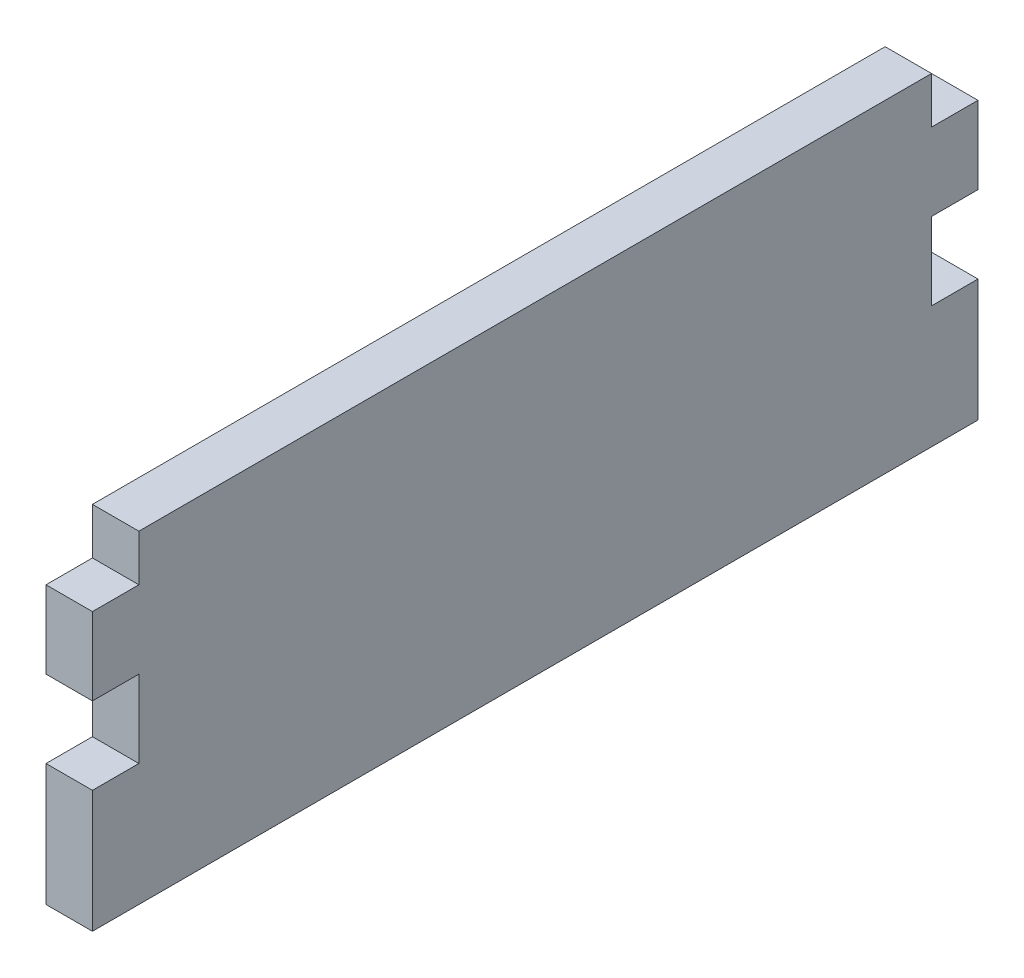
SolidWorks part; units mm, degrees
ref_plane "Спереди" through (0, 0, 0) normal (0, 0, 1) x (1, 0, 0)
ref_plane "Сверху" through (0, 0, 0) normal (0, 1, 0) x (1, 0, 0)
ref_plane "Справа" through (0, 0, 0) normal (1, 0, 0) x (0, 0, -1)
sketch "Эскиз1" plane through (0, 0, 0) normal (1, 0, 0) x (0, 0, -1)
  line L0 (-142.5825, -84.6816) -> (-136.5825, -84.6816) construction
  line L1 (-2.9825, -73.2482) -> (-105.4125, -73.2482) construction
  line L2 (7.7798, -91.3916) -> (7.7798, -95.3916) construction
  line L3 (-111.4125, -137.1716) -> (3.0175, -137.1716)
  line L4 (-2.9825, -95.3916) -> (-105.4125, -95.3916)
  line L5 (-105.4125, -95.3916) -> (-105.4125, -101.3916)
  line L6 (-105.4125, -101.3916) -> (-111.4125, -101.3916)
  line L14 (3.0175, -87.9576) -> (-2.9825, -87.9576) construction
  line L15 (-2.9825, -95.3916) -> (-2.9825, -101.3916)
  line L16 (-2.9825, -101.3916) -> (3.0175, -101.3916)
  line L17 (3.0175, -101.3916) -> (3.0175, -111.3916)
  line L18 (3.0175, -111.3916) -> (-2.9825, -111.3916)
  line L19 (-2.9825, -111.3916) -> (-2.9825, -121.3916)
  line L20 (-2.9825, -121.3916) -> (3.0175, -121.3916)
  line L21 (3.0175, -121.3916) -> (3.0175, -137.1716)
  line L22 (-111.4125, -101.3916) -> (-111.4125, -111.3916)
  line L23 (-111.4125, -111.3916) -> (-105.4125, -111.3916)
  line L24 (-105.4125, -111.3916) -> (-105.4125, -121.3916)
  line L25 (-105.4125, -121.3916) -> (-111.4125, -121.3916)
  line L26 (-111.4125, -121.3916) -> (-111.4125, -137.1716)
  point P0 (-69.7825, -114.2816)
  dimension "D1" = 6
  dimension "D2" = 102.43
  dimension "D3" = 6
  dimension "D4" = 6
  dimension "D7" = 10
  dimension "D8" = 4
extrude "Бобышка-Вытянуть1" add sketch "Эскиз1" along normal blind 6 contours L15 L16 L17 L18 L19 L20 L21 L3 L26 L25 L24 L23 L22 L6 L5 L4
